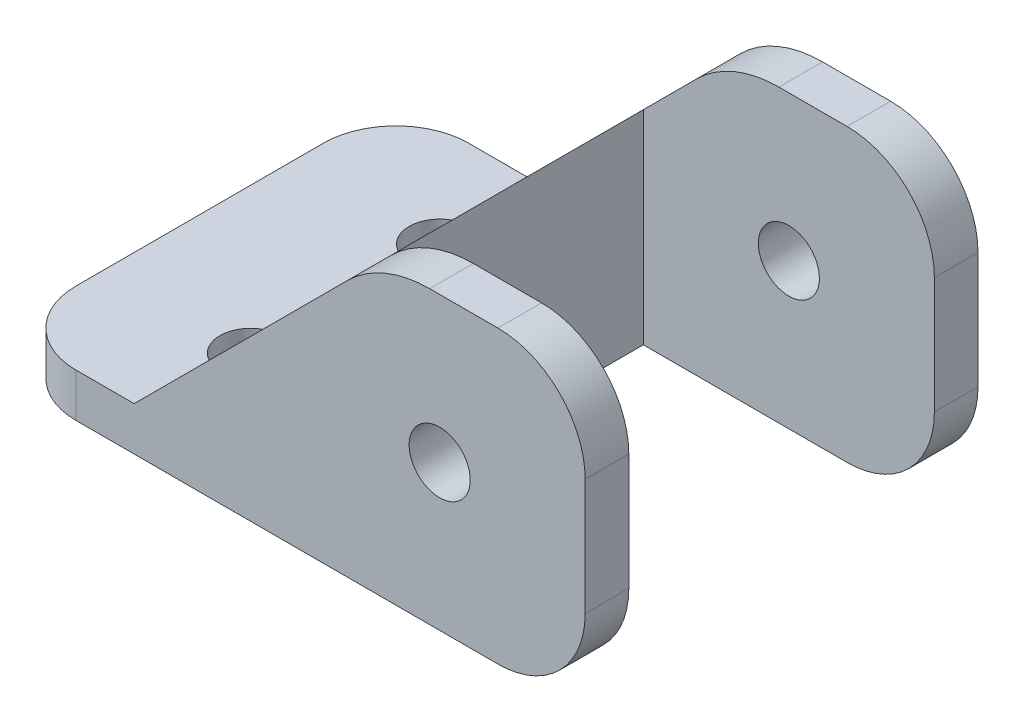
SolidWorks part; units mm, degrees
ref_plane "前视基准面" through (0, 0, 0) normal (0, 0, 1) x (1, 0, 0)
ref_plane "上视基准面" through (0, 0, 0) normal (0, 1, 0) x (1, 0, 0)
ref_plane "右视基准面" through (0, 0, 0) normal (1, 0, 0) x (0, 0, -1)
other "Configuration Table"
sketch "草图1" plane through (0, 0, 0) normal (0, 1, 0) x (1, 0, 0)
  line L1 (0, 0) -> (-15, 0)
  line L2 (0, 0) -> (0, 27)
  line L3 (0, 27) -> (-15, 27)
  line L4 (-20, 5) -> (-20, 22)
  arc A0 (-15, 0) -> (-20, 5) centre (-15, 5) cw
  arc A1 (-15, 27) -> (-20, 22) centre (-15, 22) ccw
  circle A2 centre (-10, 20) radius 2.1
  circle A3 centre (-10, 7) radius 2.1
  point P7 (-20, 0)
  point P10 (-20, 27)
  dimension "D3" = 5
  dimension "D4" = 4.2
  dimension "D7" = 4.2
  dimension "D1" = 27
  dimension "D2" = 20
  dimension "D5" = 7
  dimension "D6" = 7
  dimension "D8" = 10
  dimension "D9" = 10
extrude "凸台-拉伸1" add sketch "草图1" along normal blind 3
sketch "草图3" plane through (0, 0, 0) normal (0, 1, 0) x (1, 0, 0)
  line L0 (0, 27) -> (20, 27)
  line L1 (20, 27) -> (20, 24)
  line L2 (20, 24) -> (0, 24)
  line L3 (0, 0) -> (0, 27) construction
  line L4 (0, 24) -> (0, 27)
  line L5 (0, 0) -> (20, 0)
  line L6 (20, 0) -> (20, 3)
  line L7 (20, 3) -> (0, 3)
  line L8 (0, 3) -> (0, 0)
  dimension "D1" = 20
  dimension "D2" = 3
  dimension "D3" = 3
  dimension "D4" = 20
extrude "凸台-拉伸2" add sketch "草图3" along normal blind 20
fillet "圆角2" radius 6 4 edges at (20, 20, -1.5) (20, 0, -1.5) (20, 20, -25.5) (20, 0, -25.5)
chamfer "倒角2" distance 6 angle 45 2 edges at (0, 20, -1.5) (0, 20, -25.5)
fillet "圆角3" radius 8 2 edges at (6, 20, -1.5) (6, 20, -25.5)
sketch "草图8" plane through (0, 0, -27) normal (0, 0, -1) x (-1, 0, 0)
  line L0 (0, 14) -> (11, 3)
  line L1 (0, 3) -> (15, 3) construction
  line L2 (11, 3) -> (0, 3)
  line L3 (0, 3) -> (0, 14)
  dimension "D1" = 45
extrude "凸台-拉伸5" add sketch "草图8" against normal blind 26
sketch "草图12" plane through (0, 0, 0) normal (0, 0, 1) x (1, 0, 0)
  line L0 (20, 14) -> (20, 6) construction
  line L1 (55, 0) -> (-55, 0) construction
  circle A0 centre (10, 10) radius 2.1
  dimension "D1" = 4.2
  dimension "D2" = 10
  dimension "D3" = 10
extrude "切除-拉伸4" cut sketch "草图12" against normal blind 30
sketch "草图13" plane through (0, 3, 0) normal (0, 1, 0) x (1, 0, 0)
  circle A0 centre (-10, 20) radius 4
  circle A1 centre (-10, 7) radius 4
  dimension "D1" = 8
  dimension "D2" = 8
extrude "切除-拉伸5" cut sketch "草图13" along normal blind 30
sketch "草图14" plane through (0, 0, 0) normal (0, 0, 1) x (1, 0, 0)
  line L0 (0, 3) -> (0, 14)
  line L1 (0, 14) -> (-11, 3)
  line L2 (-11, 3) -> (0, 3)
extrude "凸台-拉伸6" add sketch "草图14" against normal blind 2
